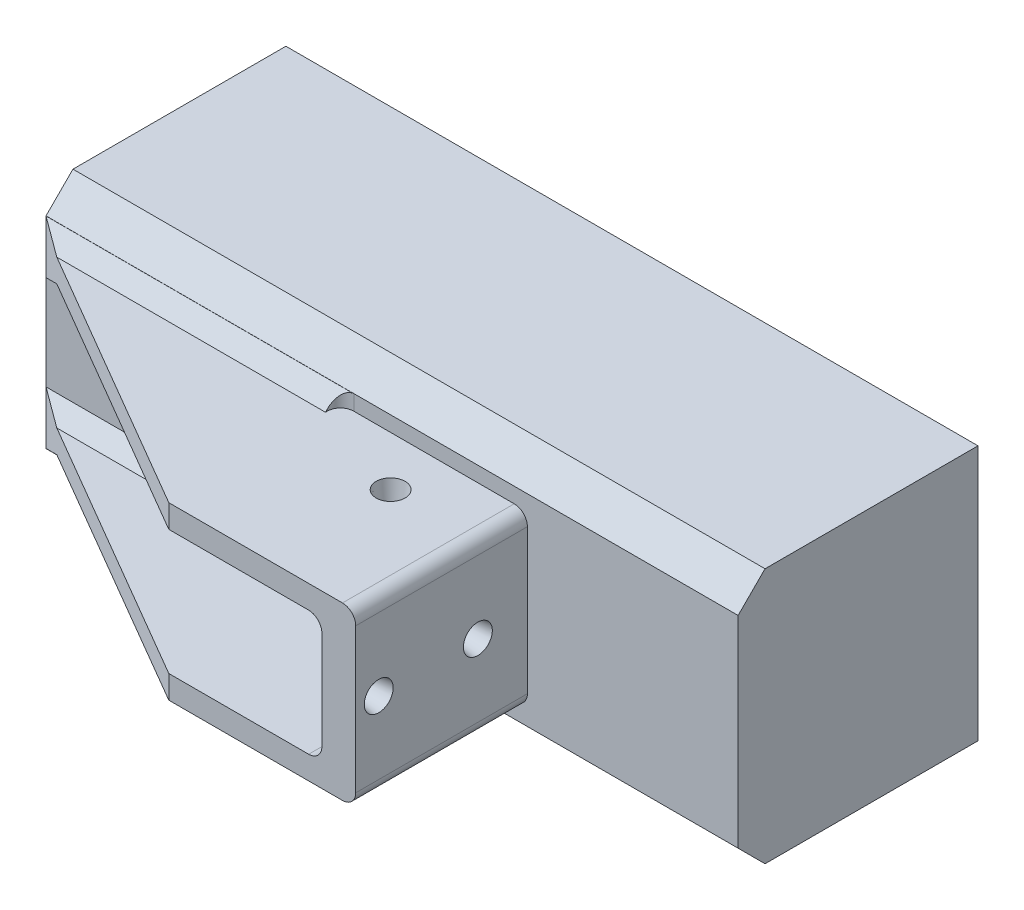
SolidWorks part; units mm, degrees
material "6061-T6 (SS)"
ref_plane "Front Plane" through (0, 0, 0) normal (0, 0, 1) x (1, 0, 0)
ref_plane "Top Plane" through (0, 0, 0) normal (0, 1, 0) x (1, 0, 0)
ref_plane "Right Plane" through (0, 0, 0) normal (1, 0, 0) x (0, 0, -1)
sketch "Sketch1" plane through (0, 0, 0) normal (0, 0, 1) x (1, 0, 0)
  line L0 (-47.5, -24.55) -> (47.5, -24.55)
  line L1 (-47.5, -24.55) -> (47.5, -24.55) construction
  line L2 (-47.5, -24.55) -> (-47.5, 24.55)
  line L3 (-47.5, 24.55) -> (47.5, 24.55) construction
  line L4 (47.5, -24.55) -> (47.5, 24.55) construction
  line L5 (0, 24.55) -> (0, -24.55) construction
  line L6 (-47.5, 0) -> (47.5, 0) construction
  line L9 (47.5, -24.55) -> (47.5, 24.55)
  line L12 (47.5, 24.55) -> (-47.5, 24.55)
  point P0 (0, 0)
  dimension "D2" = 49.1
  dimension "D1" = 95
extrude "Boss-Extrude1" add sketch "Sketch1" along normal blind 8
sketch "Sketch2" plane through (0, 0, 8) normal (0, 0, 1) x (1, 0, 0)
  line L1 (9.4, 19.05) -> (47.5, 19.05)
  line L2 (9.4, 19.05) -> (9.4, -19.05)
  line L3 (9.4, -19.05) -> (47.5, -19.05)
  line L4 (47.5, 19.05) -> (47.5, -19.05)
  line L5 (11.686, -16.764) -> (45.214, -16.764)
  line L6 (45.214, 16.764) -> (45.214, -16.764)
  line L7 (11.686, 16.764) -> (45.214, 16.764)
  line L8 (11.686, 16.764) -> (11.686, -16.764)
  line L10 (47.5, -24.55) -> (47.5, 24.55) construction
  dimension "D1" = 38.1
  dimension "D3" = 19.05
  dimension "D4" = 38.1
  dimension "D2" = 2.286
sketch "Sketch3" plane through (0, 0, 0) normal (0, 0, -1) x (-1, 0, 0)
  line L1 (47.5, -24.55) -> (37.5, -24.55)
  line L2 (47.5, -24.55) -> (47.5, 24.55)
  line L3 (47.5, 24.55) -> (37.5, 24.55)
  line L4 (37.5, -24.55) -> (37.5, 24.55)
  line L5 (-47.5, 24.55) -> (47.5, 24.55) construction
  dimension "D1" = 10
extrude "Boss-Extrude2" add sketch "Sketch3" along normal blind 38.1
sketch "Sketch4" plane through (-37.5, 0, 0) normal (1, 0, 0) x (0, 0, -1)
  line L0 (38.1, -24.55) -> (0, -24.55) construction
  line L1 (0, -24.55) -> (38.1, -24.55) construction
  line L2 (0, -24.55) -> (0, 24.55) construction
  line L3 (0, 24.55) -> (38.1, 24.55) construction
  line L4 (38.1, -24.55) -> (38.1, 24.55) construction
  line L5 (19.05, 24.55) -> (19.05, -24.55) construction
  line L6 (0, 0) -> (38.1, 0) construction
  line L7 (0, 24.55) -> (0, -24.55) construction
  line L8 (5.5796, 13.4704) -> (19.05, 0) construction
  circle A0 centre (19.05, 0) radius 11 construction
  circle A1 centre (19.05, 0) radius 19.05 construction
  circle A2 centre (19.05, 0) radius 16.71 construction
  circle A3 centre (5.5796, 13.4704) radius 1.8288
  point P0 (19.05, 0)
  dimension "D1" = 22
  dimension "D2" = 38.1
  dimension "D3" = 33.42
  dimension "D4" = 3.6576
  dimension "D5" = 45
extrude "#6 Thru Mounting hole" cut sketch "Sketch4" against normal through all
sketch "Sketch5" plane through (-37.5, 0, 0) normal (1, 0, 0) x (0, 0, -1)
  circle A0 centre (19.05, 0) radius 11
  circle A1 centre (19.05, 0) radius 11 construction
extrude "Cut-Extrude2" cut sketch "Sketch5" against normal through all
ref_axis "Motor Axis" through (-47.5, 0, -19.05) along (1, 0, 0)
pattern_circular "CirPattern1" count 4 over 360 about axis through (-47.5, 0, -19.05) along (1, 0, 0) of "#6 Thru Mounting hole"
sketch "Sketch7" plane through (0, 24.55, 0) normal (0, 1, 0) x (1, 0, 0)
  line L0 (-37.5, 38.1) -> (-37.5, 0)
  line L1 (-37.5, 0) -> (-37.5, 38.1) construction
  line L2 (47.5, 0) -> (47.5, 38.1)
  line L3 (-37.5, 0) -> (47.5, 0)
  line L4 (47.5, 38.1) -> (-37.5, 38.1)
  line L5 (47.5, 0) -> (-37.5, 0) construction
extrude "Boss-Extrude5" add sketch "Sketch7" against normal blind 5.5
mirror "Mirror1" about plane through (0, 0, 0) normal (0, 1, 0) of "Boss-Extrude5"
sketch "Sketch8" plane through (47.5, 0, 0) normal (1, 0, 0) x (0, 0, -1)
  line L0 (7.807, 15.6978) -> (9.6735, 13.8313)
  line L1 (3.3522, 11.243) -> (5.2187, 9.3765)
  line L2 (5.5796, 13.4704) -> (19.05, 0) construction
  line L3 (19.05, 0) -> (19.05, 24.55) construction
  line L4 (34.7478, 11.243) -> (32.8813, 9.3765)
  line L5 (30.293, 15.6978) -> (28.4265, 13.8313)
  line L7 (19.05, 0) -> (2.54, 0) construction
  line L8 (30.293, -15.6978) -> (28.4265, -13.8313)
  line L9 (34.7478, -11.243) -> (32.8813, -9.3765)
  line L10 (3.3522, -11.243) -> (5.2187, -9.3765)
  line L11 (7.807, -15.6978) -> (9.6735, -13.8313)
  circle A0 centre (19.05, 0) radius 16.71 construction
  arc A1 (3.3522, -15.6978) -> (4.1693, 16.4961) centre (19.4885, 0) cw
  circle A2 centre (19.05, 0) radius 22.0905 construction
  arc A3 (3.3522, 11.243) -> (7.807, 15.6978) centre (5.5796, 13.4704) cw
  arc A5 (34.7478, 11.243) -> (30.293, 15.6978) centre (32.5204, 13.4704) ccw
  arc A6 (9.6735, 13.8313) -> (28.4265, 13.8313) centre (19.05, 0) cw
  arc A7 (32.8813, 9.3765) -> (32.8813, -9.3765) centre (19.05, 0) cw
  arc A8 (5.2187, -9.3765) -> (5.2187, 9.3765) centre (19.05, 0) cw
  arc A9 (9.6735, -13.8313) -> (28.4265, -13.8313) centre (19.05, 0) ccw
  arc A10 (34.7478, -11.243) -> (30.293, -15.6978) centre (32.5204, -13.4704) cw
  arc A11 (3.3522, -11.243) -> (7.807, -15.6978) centre (5.5796, -13.4704) ccw
  line M21 (0, -19.05) -> (0, 19.05)
  dimension "D1" = 44.181
  dimension "D2" = 3.15
extrude "Cut-Extrude3" cut sketch "Sketch8" against normal offset from surface (88.81 mm away) 3.81 contours L10 A11 A1 L11 A9 L8 A10 L9 A7 L4 A5 L5 A6 L0 A3 L1 A8 | A11 L10 A8 L1 A3 A1 M21 | A1 M21 region at (47.5, 0, -19.05) region at (47.5, 0, -1.8225) region at (47.5, 0, 1.2167) up to face at (-37.5, -15.2992, -32.5204) offset beyond the face yes
fillet "Fillet1" radius 1.5 6 edges at (-39.405, -13.8313, -9.6735) (-39.405, -13.8313, -28.4265) (-39.405, -9.3765, -32.8813) (-39.405, 9.3765, -32.8813) (-39.405, 13.8313, -28.4265) (-39.405, 13.8313, -9.6735)
ref_plane "Plane1" through (0, 16.437, 0) normal (0, 1, 0) x (1, 0, 0)
sketch "Sketch14" plane through (0, 16.437, 0) normal (0, 1, 0) x (1, 0, 0)
  line L0 (45.014, -8) -> (45.014, -41)
  line L1 (-47.5, -8) -> (47.5, -8) construction
  line L2 (45.014, -41) -> (9.1, -41)
  line L3 (9.1, -41) -> (9.1, -8) construction
  line L4 (47.5, -8) -> (47.5, 38.1) construction
  line L5 (9.1, -8) -> (45.014, -8)
  line L6 (9.1, -41) -> (-47.5, -8)
  line L7 (-47.5, -8) -> (9.1, -8)
  dimension "D1" = 38.4
  dimension "D2" = 2.486
  dimension "D3" = 33
extrude "Boss-Extrude7" add sketch "Sketch14" against normal blind 4.445
mirror "Mirror2" about plane through (0, 0, 0) normal (0, 1, 0) of "Boss-Extrude7"
sketch "Sketch15" plane through (0, 0, 8) normal (0, 0, 1) x (1, 0, 0)
  line L0 (9.1, -11.992) -> (45.014, -11.992) construction
  line L1 (45.014, 11.992) -> (38.514, 11.992)
  line L2 (45.014, 11.992) -> (45.014, -11.992)
  line L3 (45.014, -11.992) -> (38.514, -11.992)
  line L4 (38.514, 11.992) -> (38.514, -11.992)
  dimension "D1" = 6.5
extrude "Boss-Extrude8" add sketch "Sketch15" along normal up to surface (33 mm away) up to face at (27.057, 14.2145, 41)
sketch "Sketch16" plane through (-37.5, 0, 0) normal (1, 0, 0) x (0, 0, -1)
  line L0 (0, 19.05) -> (0, 11.2693) construction
  line L1 (0, 11.399) -> (0, -11.399)
  circle A0 centre (19.05, 0) radius 22.2 construction
  arc A1 (0, -11.399) -> (0, 11.399) centre (19.05, 0) cw
  arc A2 (3.3522, -15.6978) -> (7.807, -15.6978) centre (5.5796, -13.4704) ccw construction
extrude "Cut-Extrude7" cut sketch "Sketch16" along normal up to surface (85 mm away) up to face at (47.5, 0, -13.3376)
sketch "Sketch17" plane through (-37.5, 0, 0) normal (1, 0, 0) x (0, 0, -1)
  line L0 (0, 11.399) -> (0, 19.05)
  line L1 (0, 19.05) -> (7.651, 19.05)
  line L2 (0, 19.05) -> (38.1, 19.05) construction
  line L3 (19.05, 0) -> (0, 0) construction
  line L4 (0, -19.05) -> (7.651, -19.05)
  line L5 (0, -11.399) -> (0, -19.05)
  arc A0 (0, 11.399) -> (7.651, 19.05) centre (19.05, 0) cw
  arc A1 (0, -11.399) -> (7.651, -19.05) centre (19.05, 0) ccw
extrude "Boss-Extrude9" add sketch "Sketch17" along normal up to surface (85 mm away) up to face at (47.5, 0, -13.325)
sketch "Sketch19" plane through (47.5, 0, 0) normal (1, 0, 0) x (0, 0, -1)
  line L7 (38.1, -19.05) -> (7.651, -19.05)
  line L8 (7.651, 19.05) -> (38.1, 19.05)
  line L9 (38.1, 19.05) -> (38.1, 24.55)
  line L10 (38.1, 24.55) -> (-8, 24.55)
  line L11 (-8, 24.55) -> (-8, -24.55)
  line L12 (-8, -24.55) -> (38.1, -24.55)
  line L13 (38.1, -24.55) -> (38.1, -19.05)
  line L14 (38.1, -19.05) -> (7.651, -19.05)
  line L15 (7.651, 19.05) -> (38.1, 19.05)
  line L16 (38.1, 19.05) -> (38.1, 24.55)
  line L17 (38.1, 24.55) -> (-8, 24.55)
  line L18 (-8, 24.55) -> (-8, -24.55)
  line L19 (-8, -24.55) -> (38.1, -24.55)
  line L20 (38.1, -24.55) -> (38.1, -19.05)
  arc A1 (7.651, 19.05) -> (7.651, -19.05) centre (19.05, 0) ccw
  arc A2 (7.651, 19.05) -> (7.651, -19.05) centre (19.05, 0) ccw
  dimension "D1" = 0
extrude "Boss-Extrude10" add sketch "Sketch19" along normal blind 30
chamfer "Chamfer3" distance 5.18 angle 45 2 edges at (15, 24.55, 8) (15, -24.55, 8)
sketch "Sketch20" plane through (0, 0, 8) normal (0, 0, 1) x (1, 0, 0)
  line L0 (38.514, -11.992) -> (-47.5, -11.992) construction
  line L1 (38.514, 11.992) -> (23.514, 11.992)
  line L2 (38.514, 11.992) -> (38.514, -11.992)
  line L3 (38.514, -11.992) -> (23.514, -11.992)
  line L4 (23.514, 11.992) -> (23.514, -11.992)
  dimension "D1" = 15
extrude "Cut-Extrude9" cut sketch "Sketch20" against normal up to next
chamfer "Chamfer4" distance 2.9 angle 45 4 edges at (-1.243, 16.437, 8) (-1.243, -16.437, 8) (-11.993, -11.992, 8) (-11.993, 11.992, 8)
sketch "Sketch21" plane through (0, 0, 41) normal (0, 0, 1) x (1, 0, 0)
  line L0 (-47.5, 19.337) -> (45.014, 19.337) construction
  line L1 (45.014, 16.437) -> (9.1, 16.437)
  line L2 (45.014, 16.437) -> (45.014, 19.337)
  line L3 (45.014, 19.337) -> (9.1, 19.337)
  line L4 (9.1, 16.437) -> (9.1, 19.337)
  line L5 (-47.5, -19.37) -> (77.5, -19.37) construction
  line L6 (45.014, -16.437) -> (9.1, -16.437)
  line L7 (45.014, -16.437) -> (45.014, -19.37)
  line L8 (45.014, -19.37) -> (9.1, -19.37)
  line L9 (9.1, -16.437) -> (9.1, -19.37)
extrude "Cut-Extrude10" cut sketch "Sketch21" against normal up to surface (33 mm away) up to face at (-11.993, 0, 8)
fillet "Fillet5" radius 2.54 8 edges at (23.514, 11.992, 5.2662) (23.514, -11.992, 5.2662) (38.514, -11.992, 20.3162) (38.514, 11.992, 20.3162) (45.014, 16.437, 24.5) (45.014, -16.437, 24.5) (9.1, 17.887, 8) (9.1, -17.887, 8)
sketch "Sketch22" plane through (45.014, 0, 0) normal (1, 0, 0) x (0, 0, -1)
  line L0 (-8, 19.37) -> (-8, -19.37) construction
  circle A0 centre (-17.525, 0) radius 2.7813
  circle A1 centre (-36.575, 0) radius 2.7813
  dimension "D1" = 5.5626
  dimension "D2" = 9.525
  dimension "D3" = 19.05
extrude "Cut-Extrude11" cut sketch "Sketch22" against normal blind 3.81 draft 8
sketch "Sketch23" plane through (41.204, 0, 0) normal (1, 0, 0) x (0, 0, -1)
  circle A0 centre (-17.525, 0) radius 2.2458 construction
  circle A1 centre (-36.575, 0) radius 2.2458 construction
  circle A2 centre (-17.525, 0) radius 2.2458
  circle A3 centre (-36.575, 0) radius 2.2458
extrude "Cut-Extrude12" cut sketch "Sketch23" against normal up to next
sketch "Sketch24" plane through (77.5, 0, 0) normal (1, 0, 0) x (0, 0, -1)
  line L0 (38.1, 19.05) -> (38.1, -19.05)
  line L9 (38.1, 24.55) -> (-2.82, 24.55)
  line L10 (-2.82, 24.55) -> (-8, 19.37)
  line L11 (-8, 19.37) -> (-8, -19.37)
  line L12 (-8, -19.37) -> (-2.82, -24.55)
  line L13 (-2.82, -24.55) -> (38.1, -24.55)
  line L14 (38.1, -24.55) -> (38.1, -19.05)
  line L15 (38.1, -19.05) -> (7.651, -19.05)
  line L16 (7.651, 19.05) -> (38.1, 19.05)
  line L17 (38.1, 19.05) -> (38.1, 24.55)
  line L18 (38.1, 24.55) -> (-2.82, 24.55)
  line L19 (-2.82, 24.55) -> (-8, 19.37)
  line L20 (-8, 19.37) -> (-8, -19.37)
  line L21 (-8, -19.37) -> (-2.82, -24.55)
  line L22 (-2.82, -24.55) -> (38.1, -24.55)
  line L23 (38.1, -24.55) -> (38.1, -19.05)
  line L24 (38.1, -19.05) -> (7.651, -19.05) construction
  line L25 (7.651, 19.05) -> (38.1, 19.05) construction
  line L26 (38.1, 19.05) -> (38.1, 24.55)
  arc A1 (7.651, 19.05) -> (7.651, -19.05) centre (19.05, 0) ccw
  arc A2 (7.651, 19.05) -> (7.651, -19.05) centre (19.05, 0) ccw construction
  dimension "D1" = 0
extrude "Boss-Extrude11" add sketch "Sketch24" along normal blind 8
sketch "Sketch25" plane through (0, -16.437, 0) normal (0, -1, 0) x (1, 0, 0)
  line L0 (45.014, 41) -> (45.014, 8) construction
  line L3 (42.474, 8) -> (11.64, 8) construction
  circle A0 centre (28.25, 17.525) radius 2.7815
  dimension "D2" = 5.563
  dimension "D1" = 16.764
  dimension "D3" = 9.525
extrude "Cut-Extrude13" cut sketch "Sketch25" against normal blind 4.064 draft 8
sketch "Sketch26" plane through (0, -12.373, 0) normal (0, -1, 0) x (1, 0, 0)
  circle A1 centre (28.25, 17.525) radius 2.2103
  circle A2 centre (28.25, 17.525) radius 2.2103
  dimension "D1" = 0
extrude "Cut-Extrude14" cut sketch "Sketch26" against normal up to next
mirror "Mirror3" about plane through (0, 0, 0) normal (0, 1, 0) of "Cut-Extrude14", "Cut-Extrude13"
equation "\"l\"= 95"
equation "\"D1@Sketch1\"=\"l\""
equation "\"h\"= 8mm"
equation "\"D1@Boss-Extrude1\"=\"h\""
equation "\"h2\"= 10mm"
equation "\"D1@Sketch3\"=\"h2\""
equation "\"l2\"= 50mm"
equation "\"h3\"= 14"
